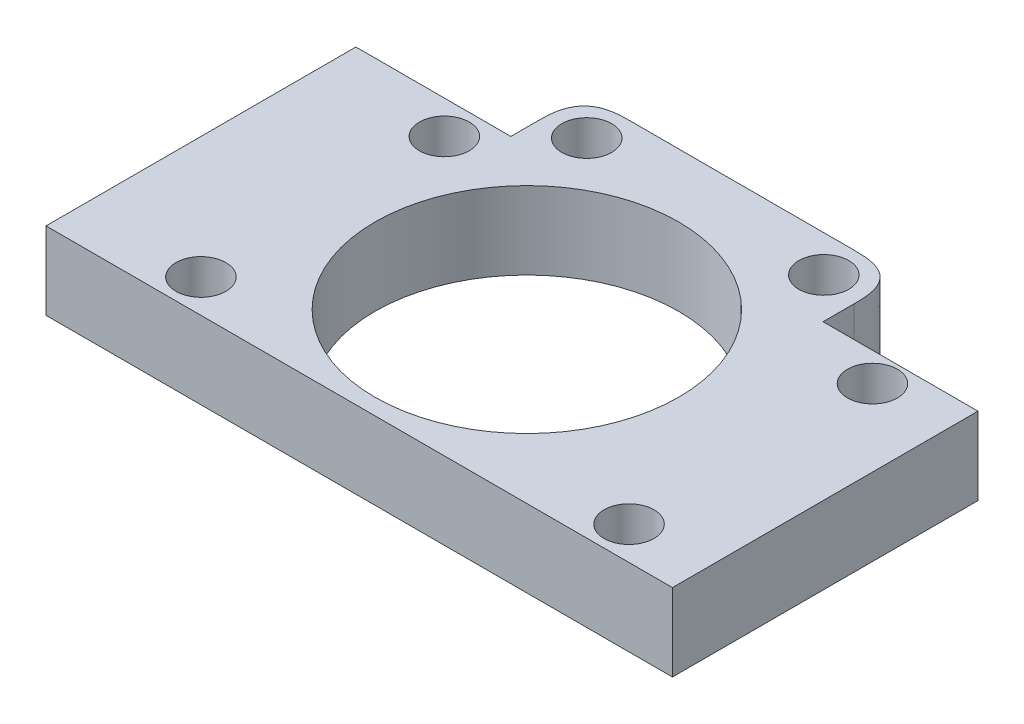
SolidWorks part; units mm, degrees
ref_plane "Alzado" through (0, 0, 0) normal (0, 0, 1) x (1, 0, 0)
ref_plane "Planta" through (0, 0, 0) normal (0, 1, 0) x (1, 0, 0)
ref_plane "Vista lateral" through (0, 0, 0) normal (1, 0, 0) x (0, 0, -1)
sketch "Croquis1" plane through (0, 0, 0) normal (0, 1, 0) x (1, 0, 0)
  line L0 (-20.193, 7.1947) -> (-10.193, 7.1947)
  line L1 (-10.193, 7.1947) -> (-10.193, 11.9147)
  line L2 (-10.193, 11.9147) -> (10.237, 11.9147)
  line L3 (10.237, 11.9147) -> (10.237, 6.9147)
  line L4 (10.237, 6.9147) -> (20.237, 6.9147)
  line L5 (20.237, 6.9147) -> (20.237, -12.8053)
  line L6 (20.237, -12.8053) -> (-20.193, -12.8053)
  line L7 (-20.193, 7.1947) -> (-20.193, -12.8053)
  line L8 (0, 14.5007) -> (0, -18.4313) construction
  line L9 (-10.193, 11.9147) -> (-0.8562, 11.9147)
  line L10 (0, 7.8347) -> (0, 11.9147)
  line L11 (0, -11.7653) -> (0, -15.8453)
  line L12 (-10.7299, 5.0497) -> (13.6801, 5.0497)
  line L13 (-12.3399, 3.4397) -> (-12.3399, -9.0503)
  line L14 (15.2901, 3.4397) -> (15.2901, -9.0503)
  line L15 (-12.3399, 6.6597) -> (-12.3399, 7.1947)
  line L16 (-10.7299, 5.0497) -> (9.8124, 5.0497)
  line L17 (-6.0435, 9.5535) -> (6.0355, 9.5535)
  circle A0 centre (0, -1.9653) radius 9.8
  circle A1 centre (-12.3399, 5.0497) radius 1.61
  circle A2 centre (-12.3399, -10.6605) radius 1.6102
  circle A3 centre (15.2901, 5.0497) radius 1.61
  circle A4 centre (15.2901, -10.6606) radius 1.6103
  circle A5 centre (-7.6538, 9.5535) radius 1.6103
  circle A6 centre (7.6458, 9.5535) radius 1.6103
  dimension "D6" = 19.6
  dimension "D13" = 3.22
  dimension "D14" = 3.22
  dimension "D15" = 3.2204
  dimension "D16" = 3.2206
  dimension "D18" = 12.0789
  dimension "D1" = 40.43
  dimension "D2" = 10
  dimension "D3" = 10
  dimension "D4" = 20
  dimension "D5" = 19.72
  dimension "D7" = 5
  dimension "D8" = 4.08
  dimension "3.16" = 4.08
  dimension "D9" = 4.72
  dimension "D10" = 24.41
  dimension "D11" = 12.49
  dimension "D12" = 12.49
  dimension "D17" = 0.535
extrude "Saliente-Extruir3" add sketch "Croquis1" along normal mid plane 5 contours A1 | A2 | L8 L16 A0 | L8 A0 L16 | A0 L8 L12 | L12 L8 A0 | A4 | A3 | A6 | A5 | L7 L6 L5 L4 L3 L2 L1 L0
fillet "Redondeo1" radius 3 3 edges at (10.237, 2.5, -9.4147) (10.237, 0, -11.9147) (10.237, -2.5, -9.4147)
fillet "Redondeo2" radius 3 3 edges at (-10.193, 0, -11.9147)
sketch "Croquis3" plane through (0, 0, 0) normal (0, 1, 0) x (1, 0, 0)
  circle A0 centre (-12.3399, 5.0497) radius 1.61
  circle A1 centre (-12.3399, -10.6605) radius 1.6102
  circle A2 centre (15.2901, 5.0497) radius 1.61
  circle A3 centre (15.2901, -10.6606) radius 1.6103
